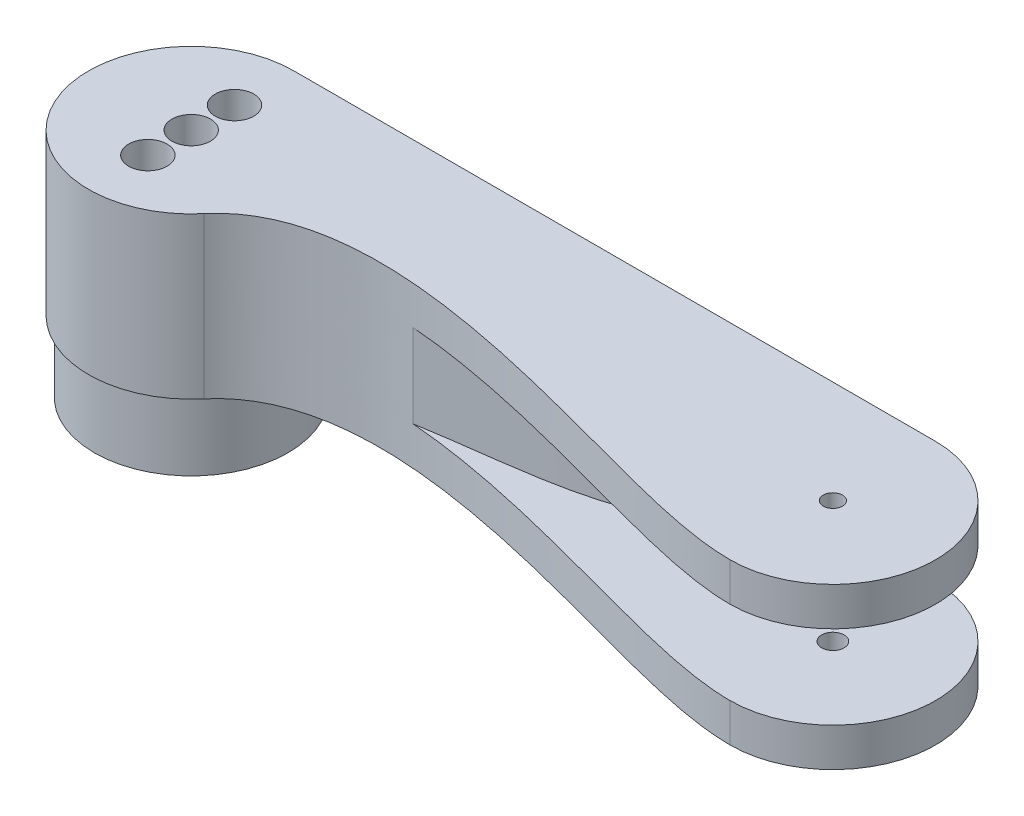
SolidWorks part; units mm, degrees
material "PLA"
ref_plane "Front Plane" through (0, 0, 0) normal (0, 0, 1) x (1, 0, 0)
ref_plane "Top Plane" through (0, 0, 0) normal (0, 1, 0) x (1, 0, 0)
ref_plane "Right Plane" through (0, 0, 0) normal (1, 0, 0) x (0, 0, -1)
sketch "Sketch1" plane through (0, 0, 0) normal (0, 1, 0) x (1, 0, 0)
  line L0 (-50, 0) -> (50, 0) construction
  line L1 (-50, 16) -> (50, 16)
  line L2 (-50, -16) -> (50, -16)
  arc A0 (-50, 16) -> (-50, -16) centre (-50, 0) ccw
  arc A1 (50, -16) -> (50, 16) centre (50, 0) ccw
  point P3 (0, 0)
  dimension "D1" = 16
  dimension "D2" = 100
extrude "Boss-Extrude1" add sketch "Sketch1" along normal blind 6
sketch "Sketch3" plane through (0, 0, 0) normal (0, -1, 0) x (1, 0, 0)
  circle A0 centre (50, 0) radius 1.75
  dimension "D1" = 3.5
extrude "Cut-Extrude2" cut sketch "Sketch3" against normal through all
sketch "Sketch4" plane through (0, 6, 0) normal (0, 1, 0) x (1, 0, 0)
  line L0 (-50, 16) -> (30, 16)
  line L1 (-50, 16) -> (50, 16) construction
  line L4 (-34.2857, -16) -> (-50, -16)
  line L5 (-50, -16) -> (50, -16) construction
  arc A0 (-50, 16) -> (-50, -16) centre (-50, 0) ccw
  arc A1 (-50, 16) -> (-50, -16) centre (-50, 0) ccw construction
  spline S0 degree 3 poles (30, 16) (21.9929, -10.8622) (-23.6763, 6.1181) (-34.2857, -16) knots 0 0 0 0 1 1 1 1
  dimension "D1" = 80
extrude "Boss-Extrude2" add sketch "Sketch4" along normal blind 13
sketch "Sketch5" plane through (0, 19, 0) normal (0, 1, 0) x (1, 0, 0)
  line L0 (-50, 0) -> (50, 0) construction
  line L1 (-50, 16) -> (50, 16)
  line L2 (-50, -16) -> (50, -16)
  arc A0 (-50, 16) -> (-50, -16) centre (-50, 0) ccw
  arc A1 (50, -16) -> (50, 16) centre (50, 0) ccw
  point P4 (0, 0)
  dimension "D1" = 16
extrude "Boss-Extrude3" add sketch "Sketch5" along normal blind 6
sketch "Sketch6" plane through (0, 25, 0) normal (0, 1, 0) x (1, 0, 0)
  circle A0 centre (50, 0) radius 1.5
  dimension "D1" = 3
extrude "Cut-Extrude3" cut sketch "Sketch6" against normal up to next
sketch "Sketch7" plane through (0, 25, 0) normal (0, 1, 0) x (1, 0, 0)
  line L0 (0, -13.75) -> (0, 13.75) construction
  line L1 (-50, -16) -> (50, -16)
  circle A0 centre (-50, 0) radius 16
  circle A1 centre (50, 0) radius 16
  spline S0 degree 3 poles (-37.7313, -10.2703) (-30.3326, -1.4318) (6.0504, -3.3646) (38.5122, -16) (50, -16) knots 0 0 0 0 0.426661 1 1 1 1
  line M5 (-50, -16) -> (50, -16)
extrude "Cut-Extrude4" cut sketch "Sketch7" against normal up to next contours S0 A0 M5 region at (-6.9153, 25, 11.0131)
sketch "Sketch8" plane through (0, 0, 0) normal (0, -1, 0) x (1, 0, 0)
  circle A1 centre (-50, 0) radius 15.1
  dimension "D1" = 30.2
extrude "Boss-Extrude4" add sketch "Sketch8" along normal blind 11
sketch "Sketch9" plane through (0, -11, 0) normal (0, -1, 0) x (1, 0, 0)
  circle A0 centre (-50, 0) radius 6.75 construction
  circle A1 centre (-50, 6.75) radius 1.75
  circle A2 centre (-50, -6.75) radius 1.75
  arc A3 (-50, 16) -> (-50, -16) centre (-50, 0) ccw construction
  point P6 (-50, 0)
  dimension "D1" = 13.5
  dimension "D2" = 3.5
extrude "Cut-Extrude5" cut sketch "Sketch9" against normal blind 10
sketch "Sketch11" plane through (0, -11, 0) normal (0, -1, 0) x (1, 0, 0)
  circle A0 centre (-50, 0) radius 3
  dimension "D1" = 6
extrude "Cut-Extrude6" cut sketch "Sketch11" against normal up to next and the other way through all
sketch "Sketch12" plane through (0, -1, 0) normal (0, -1, 0) x (1, 0, 0)
  circle A0 centre (-50, 0) radius 6.75 construction
  circle A1 centre (-50, 6.75) radius 3
  circle A2 centre (-50, -6.75) radius 3
  circle A3 centre (-50, 6.75) radius 1.75 construction
  dimension "D1" = 6
  dimension "D3" = 13.5
  dimension "D2" = 2
extrude "Cut-Extrude7" cut sketch "Sketch12" against normal up to next
equation "\"Length\"= 100mm"
equation "\"Radius\"= 14.25mm"
equation "\"Thick\"= 12mm"
equation "\"D1@Sketch1\"=16"
equation "\"D2@Sketch1\" = \"Length\""
equation "\"D1@Boss-Extrude1\"= \"Thick\""
equation "\"D1@Sketch4\"=\"Length\"*0.8"
equation "\"D1@Sketch5\"=16"
equation "\"D1@Boss-Extrude4\"=\"Thick\"-1"
